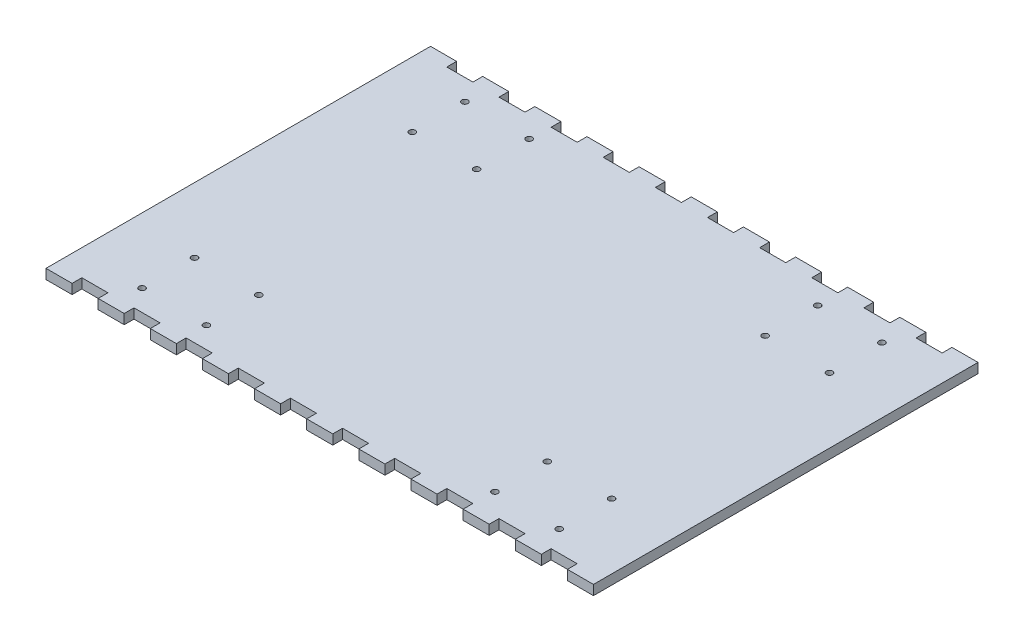
SolidWorks part; units mm, degrees
ref_plane "Front Plane" through (0, 0, 0) normal (0, 0, 1) x (1, 0, 0)
ref_plane "Top Plane" through (0, 0, 0) normal (0, 1, 0) x (1, 0, 0)
ref_plane "Right Plane" through (0, 0, 0) normal (1, 0, 0) x (0, 0, -1)
sketch "Sketch2" plane through (0, 0, 0) normal (0, 1, 0) x (1, 0, 0)
  line L11 (25.4, 88.9) -> (25.4, 93.6625)
  line L12 (12.7, -88.9) -> (25.4, -88.9)
  line L23 (0, -88.9) -> (0, 88.9)
  line L24 (12.7, 88.9) -> (25.4, 88.9)
  line L29 (266.7, -88.9) -> (266.7, 88.9)
  line L30 (25.4, 93.6625) -> (38.1, 93.6625)
  line L35 (38.1, 88.9) -> (38.1, 93.6625)
  line L41 (0, 88.9) -> (0, 93.6625)
  line L42 (0, 93.6625) -> (12.7, 93.6625)
  line L47 (12.7, 88.9) -> (12.7, 93.6625)
  line L48 (50.8, 88.9) -> (50.8, 93.6625)
  line L53 (50.8, 93.6625) -> (63.5, 93.6625)
  line L54 (63.5, 88.9) -> (63.5, 93.6625)
  line L59 (76.2, 88.9) -> (76.2, 93.6625)
  line L60 (76.2, 93.6625) -> (88.9, 93.6625)
  line L65 (88.9, 88.9) -> (88.9, 93.6625)
  line L66 (101.6, 88.9) -> (101.6, 93.6625)
  line L71 (101.6, 93.6625) -> (114.3, 93.6625)
  line L72 (114.3, 88.9) -> (114.3, 93.6625)
  line L77 (127, 88.9) -> (127, 93.6625)
  line L78 (127, 93.6625) -> (139.7, 93.6625)
  line L79 (139.7, 88.9) -> (139.7, 93.6625)
  line L80 (152.4, 88.9) -> (152.4, 93.6625)
  line L81 (152.4, 93.6625) -> (165.1, 93.6625)
  line L82 (165.1, 88.9) -> (165.1, 93.6625)
  line L83 (177.8, 88.9) -> (177.8, 93.6625)
  line L84 (177.8, 93.6625) -> (190.5, 93.6625)
  line L85 (190.5, 88.9) -> (190.5, 93.6625)
  line L86 (203.2, 88.9) -> (203.2, 93.6625)
  line L87 (203.2, 93.6625) -> (215.9, 93.6625)
  line L88 (215.9, 88.9) -> (215.9, 93.6625)
  line L89 (228.6, 88.9) -> (228.6, 93.6625)
  line L90 (228.6, 93.6625) -> (241.3, 93.6625)
  line L91 (241.3, 88.9) -> (241.3, 93.6625)
  line L92 (254, 88.9) -> (254, 93.6625)
  line L93 (254, 93.6625) -> (266.7, 93.6625)
  line L94 (266.7, 88.9) -> (266.7, 93.6625)
  line L95 (38.1, 88.9) -> (50.8, 88.9)
  line L96 (63.5, 88.9) -> (76.2, 88.9)
  line L97 (88.9, 88.9) -> (101.6, 88.9)
  line L98 (114.3, 88.9) -> (127, 88.9)
  line L99 (139.7, 88.9) -> (152.4, 88.9)
  line L100 (165.1, 88.9) -> (177.8, 88.9)
  line L101 (190.5, 88.9) -> (203.2, 88.9)
  line L102 (215.9, 88.9) -> (228.6, 88.9)
  line L103 (241.3, 88.9) -> (254, 88.9)
  line L104 (0, 0) -> (266.7, 0) construction
  line L105 (241.3, -88.9) -> (254, -88.9)
  line L106 (215.9, -88.9) -> (228.6, -88.9)
  line L107 (190.5, -88.9) -> (203.2, -88.9)
  line L108 (165.1, -88.9) -> (177.8, -88.9)
  line L109 (139.7, -88.9) -> (152.4, -88.9)
  line L110 (114.3, -88.9) -> (127, -88.9)
  line L111 (88.9, -88.9) -> (101.6, -88.9)
  line L112 (63.5, -88.9) -> (76.2, -88.9)
  line L113 (38.1, -88.9) -> (50.8, -88.9)
  line L114 (266.7, -88.9) -> (266.7, -93.6625)
  line L115 (254, -93.6625) -> (266.7, -93.6625)
  line L116 (254, -88.9) -> (254, -93.6625)
  line L117 (241.3, -88.9) -> (241.3, -93.6625)
  line L118 (228.6, -93.6625) -> (241.3, -93.6625)
  line L119 (228.6, -88.9) -> (228.6, -93.6625)
  line L120 (215.9, -88.9) -> (215.9, -93.6625)
  line L121 (203.2, -93.6625) -> (215.9, -93.6625)
  line L122 (203.2, -88.9) -> (203.2, -93.6625)
  line L123 (190.5, -88.9) -> (190.5, -93.6625)
  line L124 (177.8, -93.6625) -> (190.5, -93.6625)
  line L125 (177.8, -88.9) -> (177.8, -93.6625)
  line L126 (165.1, -88.9) -> (165.1, -93.6625)
  line L127 (152.4, -93.6625) -> (165.1, -93.6625)
  line L128 (152.4, -88.9) -> (152.4, -93.6625)
  line L129 (139.7, -88.9) -> (139.7, -93.6625)
  line L130 (127, -93.6625) -> (139.7, -93.6625)
  line L131 (127, -88.9) -> (127, -93.6625)
  line L132 (114.3, -88.9) -> (114.3, -93.6625)
  line L133 (101.6, -93.6625) -> (114.3, -93.6625)
  line L134 (101.6, -88.9) -> (101.6, -93.6625)
  line L135 (88.9, -88.9) -> (88.9, -93.6625)
  line L136 (76.2, -93.6625) -> (88.9, -93.6625)
  line L137 (76.2, -88.9) -> (76.2, -93.6625)
  line L138 (63.5, -88.9) -> (63.5, -93.6625)
  line L139 (50.8, -93.6625) -> (63.5, -93.6625)
  line L140 (50.8, -88.9) -> (50.8, -93.6625)
  line L141 (12.7, -88.9) -> (12.7, -93.6625)
  line L142 (0, -93.6625) -> (12.7, -93.6625)
  line L143 (0, -88.9) -> (0, -93.6625)
  line L144 (38.1, -88.9) -> (38.1, -93.6625)
  line L145 (25.4, -93.6625) -> (38.1, -93.6625)
  line L146 (12.7, -88.9) -> (25.4, -88.9)
  line L147 (25.4, -88.9) -> (25.4, -93.6625)
  line L148 (38.1, -88.9) -> (50.8, -88.9)
  line L149 (63.5, -88.9) -> (76.2, -88.9)
  line L150 (88.9, -88.9) -> (101.6, -88.9)
  line L151 (114.3, -88.9) -> (127, -88.9)
  line L152 (139.7, -88.9) -> (152.4, -88.9)
  line L153 (165.1, -88.9) -> (177.8, -88.9)
  line L154 (190.5, -88.9) -> (203.2, -88.9)
  line L155 (215.9, -88.9) -> (228.6, -88.9)
  line L156 (241.3, -88.9) -> (254, -88.9)
  point P68 (0, 0)
  point P69 (19.2457, -56.6773)
  point P70 (0, 0)
  dimension "D1" = 177.8
  dimension "D2" = 266.7
  dimension "D3" = 12.7
  dimension "D4" = 4.7625
extrude "Boss-Extrude1" add sketch "Sketch2" along normal blind 4.7625 contours L12 L147 L145 L144 L113 L140 L139 L138 L112 L137 L136 L135 L111 L134 L133 L132 L110 L131 L130 L129 L109 L128 L127 L126 L108 L125 L124 L123 L107 L122 L121 L120 L106 L119 L118 L117 L105 L116 L115 L114 L29 L94 L93 L92 L103 L91 L90 L89 L102 L88 L87 | L23 L104 L29 L94 L93 L92 L103 L91 L90 L89 L102 L88 L87 L86 L101 L85 L84 L83 L100 L82 L81 L80 L99 L79 L78 L77 L98 L72 L71 L66 L97 L65 L60 L59 L96 L54 L53 L48 L95 L35 L30 L11 L24 L47 L42 L41 region at (133.35, 0, -45.7283) region at (133.35, 0, 45.7283)
sketch "Sketch5" plane through (0, 4.7625, 0) normal (0, 1, 0) x (1, 0, 0)
  line L1 (25.4, 93.6625) -> (38.1, 93.6625) construction
  line L3 (0, 93.6625) -> (12.7, 93.6625) construction
  line L5 (0, 0) -> (266.7, 0) construction
  line L6 (0, -93.6625) -> (0, 93.6625) construction
  line L7 (266.7, 93.6625) -> (266.7, -93.6625) construction
  circle A0 centre (31.75, 78.6125) radius 1.5
  circle A1 centre (63.07, 78.6125) radius 1.5
  circle A2 centre (63.07, 53.0625) radius 1.5
  circle A3 centre (31.75, 53.0625) radius 1.5
  circle A20 centre (203.63, 78.6125) radius 1.5
  circle A21 centre (203.63, 53.0625) radius 1.5
  circle A22 centre (234.95, 53.0625) radius 1.5
  circle A23 centre (234.95, 78.6125) radius 1.5
  circle A24 centre (234.95, -78.6125) radius 1.5
  circle A25 centre (234.95, -53.0625) radius 1.5
  circle A26 centre (203.63, -53.0625) radius 1.5
  circle A27 centre (203.63, -78.6125) radius 1.5
  circle A28 centre (31.75, -53.0625) radius 1.5
  circle A29 centre (63.07, -53.0625) radius 1.5
  circle A30 centre (63.07, -78.6125) radius 1.5
  circle A31 centre (31.75, -78.6125) radius 1.5
  point P3 (64.57, 78.6125)
  point P7 (30.25, 78.6125)
  point P23 (31.75, 93.6625)
  point P27 (0, 0)
  point P28 (0, 0)
  point P50 (31.75, 80.1125)
  point P51 (31.75, 51.5625)
  point P52 (0, 0)
  point P53 (0, 0)
  point P54 (197.1622, 78.6125)
  point P55 (0, 0)
  dimension "D1" = 28.55
  dimension "D3" = 3
  dimension "D4" = 2
  dimension "D2" = 13.55
  dimension "D5" = 34.32
  dimension "D6" = 31.75
extrude "Cut-Extrude1" cut sketch "Sketch5" against normal through all
sketch "Sketch6" plane through (0, 4.7625, 0) normal (0, 1, 0) x (1, 0, 0)
  line L0 (0, -93.6625) -> (0, 93.6625) construction
  line L1 (0, 93.6625) -> (12.7, 93.6625) construction
  text T0 "TREY MADE THIS CHASSIS\r\n the robot will be on this\r\n<i>      -\"Danny Devito\"</i>"
  dimension "D1" = 101.6
  dimension "D2" = 82.677
